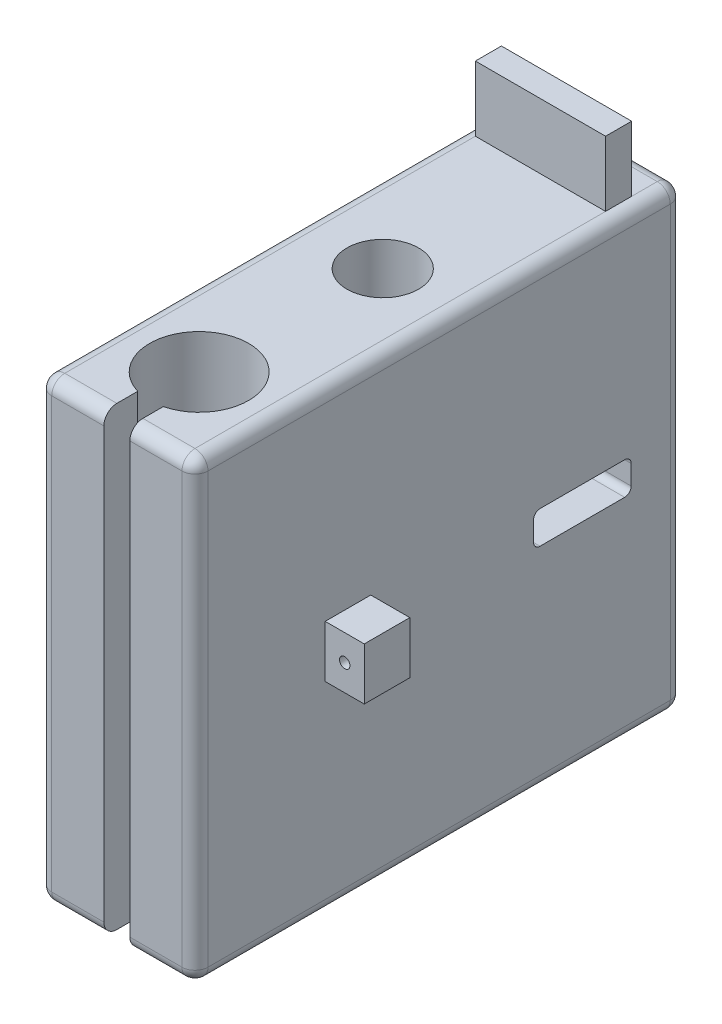
SolidWorks part; units mm, degrees
ref_plane "Front Plane" through (0, 0, 0) normal (0, 0, 1) x (1, 0, 0)
ref_plane "Top Plane" through (0, 0, 0) normal (0, 1, 0) x (1, 0, 0)
ref_plane "Right Plane" through (0, 0, 0) normal (1, 0, 0) x (0, 0, -1)
ref_plane "Plano1" through (-220, 0, 0) normal (1, 0, 0) x (0, 0, -1)
sketch "Esboço1" plane through (-220, 0, 0) normal (1, 0, 0) x (0, 0, -1)
  line L0 (-460.4999, 246.154) -> (-460.4999, 230.354) construction
  line L1 (-465.4999, 248.254) -> (-390.4999, 248.254)
  line L2 (-465.4999, 248.254) -> (-465.4999, 178.254)
  line L3 (-465.4999, 178.254) -> (-390.4999, 178.254)
  line L4 (-390.4999, 248.254) -> (-390.4999, 178.254)
  dimension "D1" = 75
  dimension "D2" = 70
  dimension "D3" = 5
extrude "Ressalto-extrusão1" add sketch "Esboço1" along normal blind 12 and the other way blind 12
sketch "Esboço3" plane through (0, 248.254, 0) normal (0, 1, 0) x (1, 0, 0)
  line L5 (-232, -465.4999) -> (-208, -465.4999) construction
  line L7 (-220, -465.4999) -> (-218, -465.4999)
  line L10 (-218, -465.4999) -> (-218, -460.3692)
  line L11 (-220, -465.4999) -> (-222, -465.4999)
  line L14 (-222, -465.4999) -> (-222, -460.292)
  arc A3 (-218, -460.3692) -> (-222, -460.292) centre (-219.8586, -452.9999) ccw
  circle A8 centre (-219.5085, -425.1499) radius 5.5
  circle A9 centre (-219.5085, -425.1499) radius 5.5
  dimension "D1" = 15.2
  dimension "D3" = 2
  dimension "D4" = 2
  dimension "D2" = 0.5
extrude "Corte-extrusão1" cut sketch "Esboço3" against normal through all
sketch "Esboço4" plane through (0, 0, 390.4999) normal (0, 0, -1) x (-1, 0, 0)
  line L0 (220, 248.254) -> (220, 178.254) construction
  line L1 (232, 248.254) -> (208, 248.254) construction
  line L2 (232, 178.254) -> (208, 178.254) construction
  circle A0 centre (219.8586, 238.254) radius 4.1
  circle A1 centre (219.8586, 188.254) radius 4.1
  dimension "D1" = 8.2
  dimension "D2" = 8.2
extrude "Corte-extrusão2" cut sketch "Esboço4" against normal blind 20
fillet "Filete1" radius 2 14 edges at (-227, 178.254, 465.4999) (-213, 178.254, 465.4999) (-213, 248.254, 465.4999) (-227, 248.254, 465.4999) (-208, 178.254, 427.9999) (-208, 248.254, 427.9999) (-208, 213.254, 465.4999) (-232, 178.254, 427.9999) (-232, 213.254, 465.4999) (-232, 248.254, 427.9999) (-220, 248.254, 390.4999) (-220, 178.254, 390.4999) (-208, 213.254, 390.4999) (-232, 213.254, 390.4999)
sketch "Esboço5" plane through (0, 0, 390.4999) normal (0, 0, -1) x (-1, 0, 0)
  line L8 (214.0123, 195.2585) -> (226.0123, 195.2487)
  line L9 (226.0123, 195.2487) -> (226.0418, 231.2487)
  line L10 (226.0418, 231.2487) -> (214.0418, 231.2585)
  line L11 (214.0418, 231.2585) -> (214.0123, 195.2585)
  line L12 (214.0123, 195.2585) -> (226.0123, 195.2487)
  line L13 (226.0123, 195.2487) -> (226.0418, 231.2487)
  line L14 (226.0418, 231.2487) -> (214.0418, 231.2585)
  line L15 (214.0418, 231.2585) -> (214.0123, 195.2585)
  dimension "D1" = 0
extrude "Corte-extrusão3" cut sketch "Esboço5" against normal blind 29
sketch "Esboço6" plane through (-232, 0, 0) normal (-1, 0, 0) x (0, 0, 1)
  line L0 (392.4999, 213.254) -> (463.4999, 213.254) construction
  line L1 (392.4999, 246.254) -> (392.4999, 180.254) construction
  line L2 (463.4999, 180.254) -> (463.4999, 246.254) construction
  line L3 (398.4999, 213.254) -> (413.4999, 213.254) construction
  line L4 (399.4999, 215.754) -> (412.4999, 215.754)
  line L5 (398.4999, 214.754) -> (398.4999, 211.754)
  line L6 (399.4999, 210.754) -> (412.4999, 210.754)
  line L7 (413.4999, 214.754) -> (413.4999, 211.754)
  arc A0 (412.4999, 215.754) -> (413.4999, 214.754) centre (412.4999, 214.754) cw
  arc A1 (412.4999, 210.754) -> (413.4999, 211.754) centre (412.4999, 211.754) ccw
  arc A2 (398.4999, 211.754) -> (399.4999, 210.754) centre (399.4999, 211.754) ccw
  arc A3 (399.4999, 215.754) -> (398.4999, 214.754) centre (399.4999, 214.754) ccw
  point P14 (413.4999, 215.754)
  point P17 (413.4999, 210.754)
  point P22 (398.4999, 215.754)
  dimension "D4" = 1
  dimension "D1" = 5
  dimension "D2" = 15
  dimension "D3" = 6
extrude "Corte-extrusão4" cut sketch "Esboço6" against normal blind 28
sketch "Esboço7" plane through (-208, 0, 0) normal (1, 0, 0) x (0, 0, -1)
  line L0 (-463.4999, 246.254) -> (-463.4999, 180.254) construction
  line L1 (-445.4999, 217.254) -> (-438.4999, 217.254)
  line L2 (-445.4999, 217.254) -> (-445.4999, 209.254)
  line L3 (-445.4999, 209.254) -> (-438.4999, 209.254)
  line L4 (-438.4999, 217.254) -> (-438.4999, 209.254)
  line L5 (-465.4999, 180.254) -> (-465.4999, 246.254) construction
  point P6 (-463.4999, 213.254)
  point P7 (-445.4999, 213.254)
  dimension "D1" = 7
  dimension "D2" = 8
  dimension "D3" = 20
extrude "Ressalto-extrusão2" add sketch "Esboço7" along normal blind 6 and the other way blind 30
ref_point "Ponto1"
sketch "Esboço9" plane through (0, 0, 445.4999) normal (0, 0, 1) x (1, 0, 0)
  line L0 (-205, 217.254) -> (-205, 209.254) construction
  line L3 (-208, 217.254) -> (-202, 217.254) construction
  line L6 (-208, 209.254) -> (-202, 209.254) construction
  line L7 (-208, 213.254) -> (-202, 213.254) construction
  line L8 (-208, 246.254) -> (-208, 180.254) construction
  line L9 (-202, 217.254) -> (-202, 209.254) construction
hole_wizard "Broca de rosquear para tarraxa de M2x0.41" positions "Esboço13" profile "Esboço14" hole size "M2x0.4" standard "Ansi Metric" end condition through all
sketch "Esboço13" plane through (0, 0, 445.4999) normal (0, 0, 1) x (1, 0, 0)
  line L0 (-205, 217.254) -> (-205, 209.254) construction
  point P0 (-205, 213.254)
sketch "Esboço14" plane through (-205, 213.254, 445.4999) normal (1, 0, 0) x (0, -1, 0)
  line L0 (0, 0) -> (0, 55)
  line L1 (0, 55) -> (0.8, 55)
  line L2 (0.8, 55) -> (0.8, 0)
  line L5 (0.8, 0) -> (0, 0)
  line L11 (0, -6.35) -> (0, 107.95) construction
  dimension "Thru Hole Dia." = 1.6
  dimension "Thru Hole Depth" = 55
sketch "Esboço15" plane through (0, 0, 445.4999) normal (0, 0, 1) x (1, 0, 0)
  line L0 (-235, 217.254) -> (-235, 209.254) construction
  line L1 (-238, 217.254) -> (-232, 217.254) construction
  line L2 (-238, 209.254) -> (-232, 209.254) construction
  line L3 (-238, 213.254) -> (-232, 213.254) construction
  line L4 (-238, 217.254) -> (-238, 209.254) construction
  line L5 (-232, 180.254) -> (-232, 246.254) construction
hole_wizard "Broca de rosquear para tarraxa de M2x0.42" positions "Esboço16" profile "Esboço17" hole size "M2x0.4" standard "Ansi Metric" end condition through all
sketch "Esboço16" plane through (0, 0, 445.4999) normal (0, 0, 1) x (1, 0, 0)
  line L0 (-235, 217.254) -> (-235, 209.254) construction
  point P0 (-235, 213.254)
sketch "Esboço17" plane through (-235, 213.254, 445.4999) normal (1, 0, 0) x (0, -1, 0)
  line L0 (0, 0) -> (0, 55)
  line L1 (0, 55) -> (0.8, 55)
  line L2 (0.8, 55) -> (0.8, 0)
  line L5 (0.8, 0) -> (0, 0)
  line L11 (0, -6.35) -> (0, 107.95) construction
  dimension "Thru Hole Dia." = 1.6
  dimension "Thru Hole Depth" = 55
sketch "Esboço18" plane through (0, 248.254, 0) normal (0, 1, 0) x (1, 0, 0)
  line L0 (-230, -392.4999) -> (-230, -463.4999) construction
  line L1 (-230, -396.4346) -> (-210, -396.4346)
  line L2 (-230, -396.4346) -> (-230, -400.4346)
  line L3 (-230, -400.4346) -> (-210, -400.4346)
  line L4 (-210, -396.4346) -> (-210, -400.4346)
  line L5 (-210, -463.4999) -> (-210, -392.4999) construction
  dimension "D1" = 4
extrude "Ressalto-extrusão3" add sketch "Esboço18" along normal blind 10
